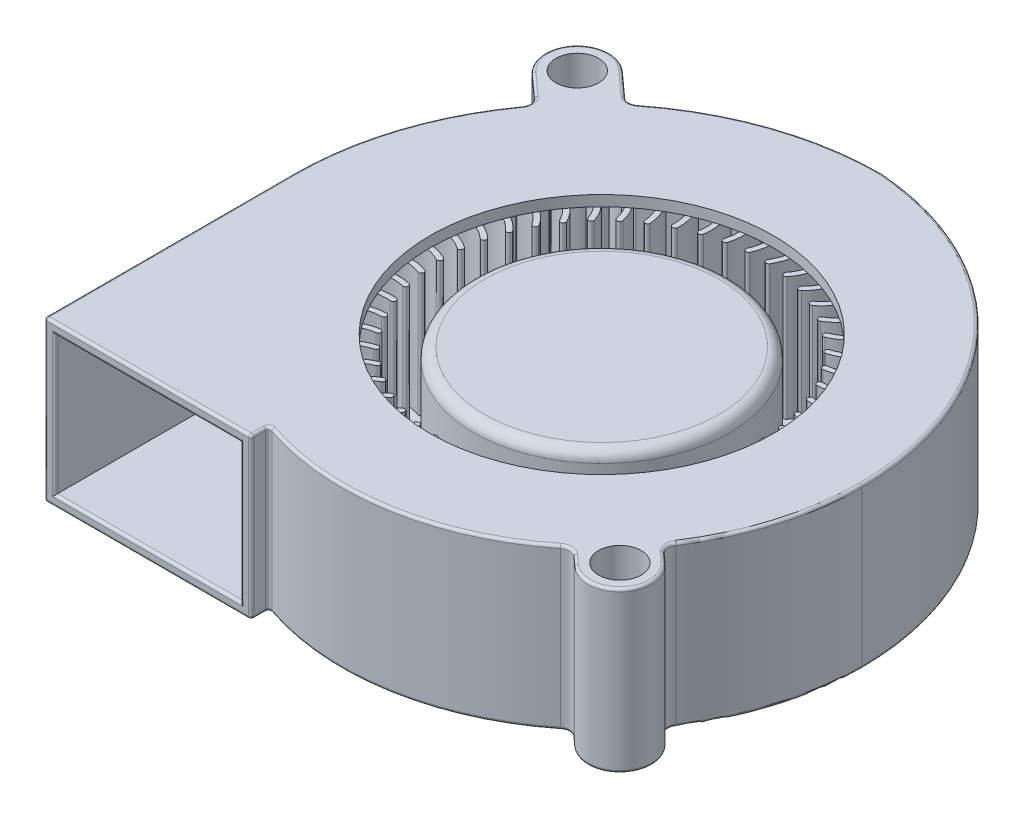
SolidWorks part; units mm, degrees
ref_plane "Front Plane" through (0, 0, 0) normal (0, 0, 1) x (1, 0, 0)
ref_plane "Top Plane" through (0, 0, 0) normal (0, 1, 0) x (1, 0, 0)
ref_plane "Right Plane" through (0, 0, 0) normal (1, 0, 0) x (0, 0, -1)
sketch "Sketch1" plane through (0, 0, 0) normal (0, 1, 0) x (1, 0, 0)
  line L0 (0, 0) -> (-22.6, 0) construction
  line L1 (0, 0) -> (-27.6, 0) construction
  line L2 (-22.6, 0) -> (-22.6, 20.3) construction
  line L4 (0, 0) -> (0, -24.7) construction
  line L5 (-8.2, -24.7) -> (-27.6, -24.7)
  line L6 (-27.6, -24.7) -> (-27.6, -1.3)
  line L7 (0, 0) -> (24.4, 0) construction
  line L8 (0, 0) -> (0, 26.3) construction
  line L10 (-8.2, -24.7) -> (-8.2, -22.9809)
  line L11 (16.5007, -19.1225) -> (17.3873, -19.9246)
  line L12 (-24.6127, 18.0754) -> (-22.5187, 16.1808)
  line L13 (-20.5873, 22.5246) -> (-18.3141, 20.468)
  line L14 (20.552, -14.6967) -> (21.4127, -15.4754)
  circle A0 centre (-22.6, 20.3) radius 2
  circle A1 centre (19.4, -17.7) radius 2
  arc A2 (17.3873, -19.9246) -> (21.4127, -15.4754) centre (19.4, -17.7) ccw
  arc A3 (0, 26.3) -> (-17.0263, 20.4224) centre (0, -1.3) ccw
  arc A4 (24.4, 0) -> (0, 26.3) centre (-1.974, 0) ccw
  arc A5 (24.4, 0) -> (20.3874, -13.4057) centre (0, 0) cw
  arc A6 (-20.5873, 22.5246) -> (-24.6127, 18.0754) centre (-22.6, 20.3) ccw
  arc A7 (15.2065, -19.082) -> (-8.2, -22.9809) centre (0, 0) cw
  circle A8 centre (0, 0) radius 16.1
  circle A9 centre (19.4, -17.7) radius 3 construction
  circle A10 centre (-22.6, 20.3) radius 3 construction
  arc A11 (-22.3788, 14.854) -> (-27.6, -1.3) centre (0, -1.3) ccw
  arc A12 (-22.3788, 14.854) -> (-22.5187, 16.1808) centre (-23.1896, 15.4392) ccw
  arc A13 (-18.3141, 20.468) -> (-17.0263, 20.4224) centre (-17.6432, 21.2095) ccw
  arc A14 (20.3874, -13.4057) -> (20.552, -14.6967) centre (21.223, -13.9551) ccw
  arc A15 (16.5007, -19.1225) -> (15.2065, -19.082) centre (15.8298, -19.864) ccw
  point P4 (-16.1, 0)
  point P29 (23.25, -20.1)
  point P32 (-16.75, 20.1)
  point P39 (19.9054, -14.1116)
  point P42 (15.8598, -18.5426)
  point P44 (0, 16.1)
  dimension "D2" = 52
  dimension "D5" = 4
  dimension "D6" = 4
  dimension "D7" = 11.5
  dimension "D12" = 19.4
  dimension "D13" = 32.2
  dimension "D15" = 1
  dimension "D8" = 44
  dimension "D3" = 45
  dimension "D4" = 47
  dimension "D9" = 10.2
  dimension "D10" = 47
  dimension "D14" = 51
  dimension "D11" = 1
extrude "BODY" add sketch "Sketch1" along normal blind 7.5 and the other way blind 7.5
shell "Shell" thickness 1 removed face at (-17.9, 0, 24.7) removed face at (0, -7.5, 16.1)
sketch "Sketch2" plane through (0, -7.5, 0) normal (0, -1, 0) x (1, 0, 0)
  circle A0 centre (0, 0) radius 20.1
extrude "Boss-Extrude2" add sketch "Sketch2" against normal blind 1
ref_plane "Plane1" through (0, -6.3, 0) normal (0, 1, 0) x (1, 0, 0)
sketch "Sketch3" plane through (0, -6.3, 0) normal (0, 1, 0) x (1, 0, 0)
  circle A0 centre (0, 0) radius 12
  dimension "D1" = 24
extrude "MOTOR" add sketch "Sketch3" along normal up to surface (12.8 mm away) separate body up to face at (-5.8935, 6.5, -0.0119)
ref_axis "Axis1" through (0, 6.5, 0) along (0, -1, 0)
fillet "Fillet1" radius 1 1 edges at (0, 6.5, -12)
fillet "Fillet2" radius 0.25 43 edges at (4.0092, -7.5, 24.0684) (16.944, -7.5, 19.5235) (21.6246, -7.5, 19.7127) (20.9824, -7.5, 15.086) (23.3753, -7.5, 6.9967) (17.3606, -7.5, -17.9377) (-9.0061, -7.5, -24.7893) (-19.4507, -7.5, -21.4963) (-24.8246, -7.5, -22.3127) (-23.5657, -7.5, -17.1281) (-26.2623, -7.5, -7.1884) (-27.6, -7.5, 13) (-19.4507, 7.5, -21.4963) (-24.8246, 7.5, -22.3127) (-26.2623, 7.5, -7.1884) (-27.6, 0, 24.7) (-26.6, 0, 24.7) (-17.9, 6.5, 24.7) (-9.2, 0, 24.7) (-17.9, -6.5, 24.7) (-17.9, -7.5, 24.7) (-8.2, -7.5, 23.8404) (-8.2, 0, 22.9809) (-8.2, 0, 24.7) (-17.9, 7.5, 24.7) (-8.2, 7.5, 23.8404) (4.0092, 7.5, 24.0684) (16.944, 7.5, 19.5235) (21.6246, 7.5, 19.7127) (20.9824, 7.5, 15.086) (23.3753, 7.5, 6.9967) (17.3606, 7.5, -17.9377) (-9.0061, 7.5, -24.7893) (-23.5657, 7.5, -17.1281) (-27.6, 7.5, 13) (15.8611, -7.5, 18.8645) (20.231, -7.5, 14.0816) (-17.6785, -7.5, -20.2101) (-22.1951, -7.5, -15.5441) (15.8611, 7.5, 18.8645) (20.231, 7.5, 14.0816) (-17.6785, 7.5, -20.2101) (-22.1951, 7.5, -15.5441)
sketch "Sketch9" plane through (0, -6.3, 0) normal (0, 1, 0) x (1, 0, 0)
  circle A0 centre (0, 0) radius 19
  dimension "D1" = 38
extrude "BLADE BASE" add sketch "Sketch9" along normal blind 1 separate body
sketch "Sketch10" plane through (0, -5.3, 0) normal (0, 1, 0) x (1, 0, 0)
  line L0 (0, 0) -> (-18.8663, 0) construction
  line L1 (-16.8663, 0.5) -> (-16.8663, 0) construction
  line L2 (-14.8663, 0) -> (-15.1016, -0.4412) construction
  line L3 (-18.8663, 0) -> (-18.6311, -0.4412) construction
  arc A1 (-18.8663, 0) -> (-14.8663, 0) centre (-16.8663, -3.75) cw
  arc A2 (-18.6311, -0.4412) -> (-15.1016, -0.4412) centre (-16.8663, -3.75) cw
  arc A3 (-18.8663, 0) -> (-18.6311, -0.4412) centre (-18.7487, -0.2206) ccw
  arc A4 (-15.1016, -0.4412) -> (-14.8663, 0) centre (-14.984, -0.2206) ccw
  circle A5 centre (0, 0) radius 19 construction
  arc A6 (-18.7176, 2.3646) -> (-18.5394, 1.8974) centre (-18.6285, 2.131) ccw
  arc A7 (-18.7176, 2.3646) -> (-14.7491, 1.8632) centre (-17.2034, -1.6065) cw
  arc A8 (-18.5394, 1.8974) -> (-15.0379, 1.455) centre (-17.2034, -1.6065) cw
  arc A9 (-15.0379, 1.455) -> (-14.7491, 1.8632) centre (-14.8935, 1.6591) ccw
  arc A10 (-18.2736, 4.6919) -> (-18.1554, 4.206) centre (-18.2145, 4.449) ccw
  arc A11 (-18.2736, 4.6919) -> (-14.3993, 3.6971) centre (-17.269, 0.5623) cw
  arc A12 (-18.1554, 4.206) -> (-14.7369, 3.3283) centre (-17.269, 0.5623) cw
  arc A13 (-14.7369, 3.3283) -> (-14.3993, 3.6971) centre (-14.5681, 3.5127) ccw
  arc A14 (-17.5415, 6.9452) -> (-17.4851, 6.4484) centre (-17.5133, 6.6968) ccw
  arc A15 (-17.5415, 6.9452) -> (-13.8224, 5.4727) centre (-17.0624, 2.7223) cw
  arc A16 (-17.4851, 6.4484) -> (-14.2036, 5.1491) centre (-17.0624, 2.7223) cw
  arc A17 (-14.2036, 5.1491) -> (-13.8224, 5.4727) centre (-14.013, 5.3109) ccw
  arc A18 (-16.5327, 9.0889) -> (-16.5391, 8.589) centre (-16.5359, 8.839) ccw
  arc A19 (-16.5327, 9.0889) -> (-13.0275, 7.1619) centre (-16.5867, 4.8393) cw
  arc A20 (-16.5391, 8.589) -> (-13.4462, 6.8887) centre (-16.5867, 4.8393) cw
  arc A21 (-13.4462, 6.8887) -> (-13.0275, 7.1619) centre (-13.2368, 7.0253) ccw
  arc A22 (-15.2632, 11.0894) -> (-15.3322, 10.5941) centre (-15.2977, 10.8418) ccw
  arc A23 (-15.2632, 11.0894) -> (-12.0271, 8.7382) centre (-15.8494, 6.88) cw
  arc A24 (-15.3322, 10.5941) -> (-12.4768, 8.5196) centre (-15.8494, 6.88) cw
  arc A25 (-12.4768, 8.5196) -> (-12.0271, 8.7382) centre (-12.252, 8.6289) ccw
  arc A26 (-13.753, 12.9149) -> (-13.8835, 12.4322) centre (-13.8182, 12.6736) ccw
  arc A27 (-13.753, 12.9149) -> (-10.8371, 10.1767) centre (-14.8621, 8.8122) cw
  arc A28 (-13.8835, 12.4322) -> (-11.3106, 10.0162) centre (-14.8621, 8.8122) cw
  arc A29 (-11.3106, 10.0162) -> (-10.8371, 10.1767) centre (-11.0739, 10.0964) ccw
  arc A30 (-12.0259, 14.5368) -> (-12.2158, 14.0743) centre (-12.1208, 14.3055) ccw
  arc A31 (-12.0259, 14.5368) -> (-9.4762, 11.4547) centre (-13.6404, 10.6054) cw
  arc A32 (-12.2158, 14.0743) -> (-9.9661, 11.3548) centre (-13.6404, 10.6054) cw
  arc A33 (-9.9661, 11.3548) -> (-9.4762, 11.4547) centre (-9.7211, 11.4048) ccw
  arc A34 (-10.1091, 15.9294) -> (-10.3555, 15.4943) centre (-10.2323, 15.7119) ccw
  arc A35 (-10.1091, 15.9294) -> (-7.9658, 12.5521) centre (-12.2037, 12.2314) cw
  arc A36 (-10.3555, 15.4943) -> (-8.4644, 12.5143) centre (-12.2037, 12.2314) cw
  arc A37 (-8.4644, 12.5143) -> (-7.9658, 12.5521) centre (-8.2151, 12.5332) ccw
  arc A38 (-8.0329, 17.0708) -> (-8.3319, 16.67) centre (-8.1824, 16.8704) ccw
  arc A39 (-8.0329, 17.0708) -> (-6.3298, 13.4515) centre (-10.5744, 13.6645) cw
  arc A40 (-8.3319, 16.67) -> (-6.8292, 13.4765) centre (-10.5744, 13.6645) cw
  arc A41 (-6.8292, 13.4765) -> (-6.3298, 13.4515) centre (-6.5795, 13.464) ccw
  arc A42 (-5.83, 17.943) -> (-6.1769, 17.5829) centre (-6.0035, 17.7629) ccw
  arc A43 (-5.83, 17.943) -> (-4.594, 14.1387) centre (-8.7785, 14.882) cw
  arc A44 (-6.1769, 17.5829) -> (-5.0862, 14.2262) centre (-8.7785, 14.882) cw
  arc A45 (-5.0862, 14.2262) -> (-4.594, 14.1387) centre (-4.8401, 14.1825) ccw
  arc A46 (-3.5352, 18.5322) -> (-3.9245, 18.2184) centre (-3.7298, 18.3753) ccw
  arc A47 (-3.5352, 18.5322) -> (-2.7857, 14.603) centre (-6.844, 15.8649) cw
  arc A48 (-3.9245, 18.2184) -> (-3.2631, 14.7515) centre (-6.844, 15.8649) cw
  arc A49 (-3.2631, 14.7515) -> (-2.7857, 14.603) centre (-3.0244, 14.6773) ccw
  arc A50 (-1.1846, 18.8291) -> (-1.6102, 18.5666) centre (-1.3974, 18.6979) ccw
  arc A51 (-1.1846, 18.8291) -> (-0.9335, 14.837) centre (-4.8016, 16.5976) cw
  arc A52 (-1.6102, 18.5666) -> (-1.3885, 15.0441) centre (-4.8016, 16.5976) cw
  arc A53 (-1.3885, 15.0441) -> (-0.9335, 14.837) centre (-1.161, 14.9406) ccw
  arc A54 (1.1846, 18.8291) -> (0.7295, 18.622) centre (0.9571, 18.7256) ccw
  arc A55 (1.1846, 18.8291) -> (0.9335, 14.837) centre (-2.6836, 17.0685) cw
  arc A56 (0.7295, 18.622) -> (0.5079, 15.0995) centre (-2.6836, 17.0685) cw
  arc A57 (0.5079, 15.0995) -> (0.9335, 14.837) centre (0.7207, 14.9683) ccw
  arc A58 (3.5352, 18.5322) -> (3.0577, 18.3837) centre (3.2965, 18.4579) ccw
  arc A59 (3.5352, 18.5322) -> (2.7857, 14.603) centre (-0.5231, 17.2703) cw
  arc A60 (3.0577, 18.3837) -> (2.3964, 14.9168) centre (-0.5231, 17.2703) cw
  arc A61 (2.3964, 14.9168) -> (2.7857, 14.603) centre (2.591, 14.7599) ccw
  arc A62 (5.83, 17.943) -> (5.3377, 17.8555) centre (5.5839, 17.8992) ccw
  arc A63 (5.83, 17.943) -> (4.594, 14.1387) centre (1.6455, 17.1997) cw
  arc A64 (5.3377, 17.8555) -> (4.2471, 14.4988) centre (1.6455, 17.1997) cw
  arc A65 (4.2471, 14.4988) -> (4.594, 14.1387) centre (4.4205, 14.3188) ccw
  arc A66 (8.0329, 17.0708) -> (7.5335, 17.0457) centre (7.7832, 17.0583) ccw
  arc A67 (8.0329, 17.0708) -> (6.3298, 13.4515) centre (3.7882, 16.8578) cw
  arc A68 (7.5335, 17.0457) -> (6.0308, 13.8522) centre (3.7882, 16.8578) cw
  arc A69 (6.0308, 13.8522) -> (6.3298, 13.4515) centre (6.1803, 13.6518) ccw
  arc A70 (10.1091, 15.9294) -> (9.6105, 15.9671) centre (9.8598, 15.9483) ccw
  arc A71 (10.1091, 15.9294) -> (7.9658, 12.5521) centre (5.8712, 16.2501) cw
  arc A72 (9.6105, 15.9671) -> (7.7194, 12.9871) centre (5.8712, 16.2501) cw
  arc A73 (7.7194, 12.9871) -> (7.9658, 12.5521) centre (7.8426, 12.7696) ccw
  arc A74 (12.0259, 14.5368) -> (11.5359, 14.6367) centre (11.7809, 14.5867) ccw
  arc A75 (12.0259, 14.5368) -> (9.4762, 11.4547) centre (7.8616, 15.3861) cw
  arc A76 (11.5359, 14.6367) -> (9.2862, 11.9172) centre (7.8616, 15.3861) cw
  arc A77 (9.2862, 11.9172) -> (9.4762, 11.4547) centre (9.3812, 11.686) ccw
  arc A78 (13.753, 12.9149) -> (13.2794, 13.0754) centre (13.5162, 12.9952) ccw
  arc A79 (13.753, 12.9149) -> (10.8371, 10.1767) centre (9.728, 14.2794) cw
  arc A80 (13.2794, 13.0754) -> (10.7066, 10.6594) centre (9.728, 14.2794) cw
  arc A81 (10.7066, 10.6594) -> (10.8371, 10.1767) centre (10.7719, 10.4181) ccw
  arc A82 (15.2632, 11.0894) -> (14.8135, 11.308) centre (15.0384, 11.1987) ccw
  arc A83 (15.2632, 11.0894) -> (12.0271, 8.7382) centre (11.441, 12.9476) cw
  arc A84 (14.8135, 11.308) -> (11.9582, 9.2334) centre (11.441, 12.9476) cw
  arc A85 (11.9582, 9.2334) -> (12.0271, 8.7382) centre (11.9926, 8.9858) ccw
  arc A86 (16.5327, 9.0889) -> (16.114, 9.3622) centre (16.3233, 9.2256) ccw
  arc A87 (16.5327, 9.0889) -> (13.0275, 7.1619) centre (12.9735, 11.4116) cw
  arc A88 (16.114, 9.3622) -> (13.0211, 7.6619) centre (12.9735, 11.4116) cw
  arc A89 (13.0211, 7.6619) -> (13.0275, 7.1619) centre (13.0243, 7.4119) ccw
  arc A90 (17.5415, 6.9452) -> (17.1603, 7.2687) centre (17.3509, 7.107) ccw
  arc A91 (17.5415, 6.9452) -> (13.8224, 5.4727) centre (14.3015, 9.6956) cw
  arc A92 (17.1603, 7.2687) -> (13.8787, 5.9695) centre (14.3015, 9.6956) cw
  arc A93 (13.8787, 5.9695) -> (13.8224, 5.4727) centre (13.8506, 5.7211) ccw
  arc A94 (18.2736, 4.6919) -> (17.936, 5.0607) centre (18.1048, 4.8763) ccw
  arc A95 (18.2736, 4.6919) -> (14.3993, 3.6971) centre (15.4039, 7.8267) cw
  arc A96 (17.936, 5.0607) -> (14.5175, 4.1829) centre (15.4039, 7.8267) cw
  arc A97 (14.5175, 4.1829) -> (14.3993, 3.6971) centre (14.4584, 3.94) ccw
  arc A98 (18.7176, 2.3646) -> (18.4288, 2.7728) centre (18.5732, 2.5687) ccw
  arc A99 (18.7176, 2.3646) -> (14.7491, 1.8632) centre (16.2634, 5.8343) cw
  arc A100 (18.4288, 2.7728) -> (14.9273, 2.3304) centre (16.2634, 5.8343) cw
  arc A101 (14.9273, 2.3304) -> (14.7491, 1.8632) centre (14.8382, 2.0968) ccw
  arc A102 (18.8663, 0) -> (18.6311, 0.4412) centre (18.7487, 0.2206) ccw
  arc A103 (18.8663, 0) -> (14.8663, 0) centre (16.8663, 3.75) cw
  arc A104 (18.6311, 0.4412) -> (15.1016, 0.4412) centre (16.8663, 3.75) cw
  arc A105 (15.1016, 0.4412) -> (14.8663, 0) centre (14.984, 0.2206) ccw
  arc A106 (18.7176, -2.3646) -> (18.5394, -1.8974) centre (18.6285, -2.131) ccw
  arc A107 (18.7176, -2.3646) -> (14.7491, -1.8632) centre (17.2034, 1.6065) cw
  arc A108 (18.5394, -1.8974) -> (15.0379, -1.455) centre (17.2034, 1.6065) cw
  arc A109 (15.0379, -1.455) -> (14.7491, -1.8632) centre (14.8935, -1.6591) ccw
  arc A110 (18.2736, -4.6919) -> (18.1554, -4.206) centre (18.2145, -4.449) ccw
  arc A111 (18.2736, -4.6919) -> (14.3993, -3.6971) centre (17.269, -0.5623) cw
  arc A112 (18.1554, -4.206) -> (14.7369, -3.3283) centre (17.269, -0.5623) cw
  arc A113 (14.7369, -3.3283) -> (14.3993, -3.6971) centre (14.5681, -3.5127) ccw
  arc A114 (17.5415, -6.9452) -> (17.4851, -6.4484) centre (17.5133, -6.6968) ccw
  arc A115 (17.5415, -6.9452) -> (13.8224, -5.4727) centre (17.0624, -2.7223) cw
  arc A116 (17.4851, -6.4484) -> (14.2036, -5.1491) centre (17.0624, -2.7223) cw
  arc A117 (14.2036, -5.1491) -> (13.8224, -5.4727) centre (14.013, -5.3109) ccw
  arc A118 (16.5327, -9.0889) -> (16.5391, -8.589) centre (16.5359, -8.839) ccw
  arc A119 (16.5327, -9.0889) -> (13.0275, -7.1619) centre (16.5867, -4.8393) cw
  arc A120 (16.5391, -8.589) -> (13.4462, -6.8887) centre (16.5867, -4.8393) cw
  arc A121 (13.4462, -6.8887) -> (13.0275, -7.1619) centre (13.2368, -7.0253) ccw
  arc A122 (15.2632, -11.0894) -> (15.3322, -10.5941) centre (15.2977, -10.8418) ccw
  arc A123 (15.2632, -11.0894) -> (12.0271, -8.7382) centre (15.8494, -6.88) cw
  arc A124 (15.3322, -10.5941) -> (12.4768, -8.5196) centre (15.8494, -6.88) cw
  arc A125 (12.4768, -8.5196) -> (12.0271, -8.7382) centre (12.252, -8.6289) ccw
  arc A126 (13.753, -12.9149) -> (13.8835, -12.4322) centre (13.8182, -12.6736) ccw
  arc A127 (13.753, -12.9149) -> (10.8371, -10.1767) centre (14.8621, -8.8122) cw
  arc A128 (13.8835, -12.4322) -> (11.3106, -10.0162) centre (14.8621, -8.8122) cw
  arc A129 (11.3106, -10.0162) -> (10.8371, -10.1767) centre (11.0739, -10.0964) ccw
  arc A130 (12.0259, -14.5368) -> (12.2158, -14.0743) centre (12.1208, -14.3055) ccw
  arc A131 (12.0259, -14.5368) -> (9.4762, -11.4547) centre (13.6404, -10.6054) cw
  arc A132 (12.2158, -14.0743) -> (9.9661, -11.3548) centre (13.6404, -10.6054) cw
  arc A133 (9.9661, -11.3548) -> (9.4762, -11.4547) centre (9.7211, -11.4048) ccw
  arc A134 (10.1091, -15.9294) -> (10.3555, -15.4943) centre (10.2323, -15.7119) ccw
  arc A135 (10.1091, -15.9294) -> (7.9658, -12.5521) centre (12.2037, -12.2314) cw
  arc A136 (10.3555, -15.4943) -> (8.4644, -12.5143) centre (12.2037, -12.2314) cw
  arc A137 (8.4644, -12.5143) -> (7.9658, -12.5521) centre (8.2151, -12.5332) ccw
  arc A138 (8.0329, -17.0708) -> (8.3319, -16.67) centre (8.1824, -16.8704) ccw
  arc A139 (8.0329, -17.0708) -> (6.3298, -13.4515) centre (10.5744, -13.6645) cw
  arc A140 (8.3319, -16.67) -> (6.8292, -13.4765) centre (10.5744, -13.6645) cw
  arc A141 (6.8292, -13.4765) -> (6.3298, -13.4515) centre (6.5795, -13.464) ccw
  arc A142 (5.83, -17.943) -> (6.1769, -17.5829) centre (6.0035, -17.7629) ccw
  arc A143 (5.83, -17.943) -> (4.594, -14.1387) centre (8.7785, -14.882) cw
  arc A144 (6.1769, -17.5829) -> (5.0862, -14.2262) centre (8.7785, -14.882) cw
  arc A145 (5.0862, -14.2262) -> (4.594, -14.1387) centre (4.8401, -14.1825) ccw
  arc A146 (3.5352, -18.5322) -> (3.9245, -18.2184) centre (3.7298, -18.3753) ccw
  arc A147 (3.5352, -18.5322) -> (2.7857, -14.603) centre (6.844, -15.8649) cw
  arc A148 (3.9245, -18.2184) -> (3.2631, -14.7515) centre (6.844, -15.8649) cw
  arc A149 (3.2631, -14.7515) -> (2.7857, -14.603) centre (3.0244, -14.6773) ccw
  arc A150 (1.1846, -18.8291) -> (1.6102, -18.5666) centre (1.3974, -18.6979) ccw
  arc A151 (1.1846, -18.8291) -> (0.9335, -14.837) centre (4.8016, -16.5976) cw
  arc A152 (1.6102, -18.5666) -> (1.3885, -15.0441) centre (4.8016, -16.5976) cw
  arc A153 (1.3885, -15.0441) -> (0.9335, -14.837) centre (1.161, -14.9406) ccw
  arc A154 (-1.1846, -18.8291) -> (-0.7295, -18.622) centre (-0.9571, -18.7256) ccw
  arc A155 (-1.1846, -18.8291) -> (-0.9335, -14.837) centre (2.6836, -17.0685) cw
  arc A156 (-0.7295, -18.622) -> (-0.5079, -15.0995) centre (2.6836, -17.0685) cw
  arc A157 (-0.5079, -15.0995) -> (-0.9335, -14.837) centre (-0.7207, -14.9683) ccw
  arc A158 (-3.5352, -18.5322) -> (-3.0577, -18.3837) centre (-3.2965, -18.4579) ccw
  arc A159 (-3.5352, -18.5322) -> (-2.7857, -14.603) centre (0.5231, -17.2703) cw
  arc A160 (-3.0577, -18.3837) -> (-2.3964, -14.9168) centre (0.5231, -17.2703) cw
  arc A161 (-2.3964, -14.9168) -> (-2.7857, -14.603) centre (-2.591, -14.7599) ccw
  arc A162 (-5.83, -17.943) -> (-5.3377, -17.8555) centre (-5.5839, -17.8992) ccw
  arc A163 (-5.83, -17.943) -> (-4.594, -14.1387) centre (-1.6455, -17.1997) cw
  arc A164 (-5.3377, -17.8555) -> (-4.2471, -14.4988) centre (-1.6455, -17.1997) cw
  arc A165 (-4.2471, -14.4988) -> (-4.594, -14.1387) centre (-4.4205, -14.3188) ccw
  arc A166 (-8.0329, -17.0708) -> (-7.5335, -17.0457) centre (-7.7832, -17.0583) ccw
  arc A167 (-8.0329, -17.0708) -> (-6.3298, -13.4515) centre (-3.7882, -16.8578) cw
  arc A168 (-7.5335, -17.0457) -> (-6.0308, -13.8522) centre (-3.7882, -16.8578) cw
  arc A169 (-6.0308, -13.8522) -> (-6.3298, -13.4515) centre (-6.1803, -13.6518) ccw
  arc A170 (-10.1091, -15.9294) -> (-9.6105, -15.9671) centre (-9.8598, -15.9483) ccw
  arc A171 (-10.1091, -15.9294) -> (-7.9658, -12.5521) centre (-5.8712, -16.2501) cw
  arc A172 (-9.6105, -15.9671) -> (-7.7194, -12.9871) centre (-5.8712, -16.2501) cw
  arc A173 (-7.7194, -12.9871) -> (-7.9658, -12.5521) centre (-7.8426, -12.7696) ccw
  arc A174 (-12.0259, -14.5368) -> (-11.5359, -14.6367) centre (-11.7809, -14.5867) ccw
  arc A175 (-12.0259, -14.5368) -> (-9.4762, -11.4547) centre (-7.8616, -15.3861) cw
  arc A176 (-11.5359, -14.6367) -> (-9.2862, -11.9172) centre (-7.8616, -15.3861) cw
  arc A177 (-9.2862, -11.9172) -> (-9.4762, -11.4547) centre (-9.3812, -11.686) ccw
  arc A178 (-13.753, -12.9149) -> (-13.2794, -13.0754) centre (-13.5162, -12.9952) ccw
  arc A179 (-13.753, -12.9149) -> (-10.8371, -10.1767) centre (-9.728, -14.2794) cw
  arc A180 (-13.2794, -13.0754) -> (-10.7066, -10.6594) centre (-9.728, -14.2794) cw
  arc A181 (-10.7066, -10.6594) -> (-10.8371, -10.1767) centre (-10.7719, -10.4181) ccw
  arc A182 (-15.2632, -11.0894) -> (-14.8135, -11.308) centre (-15.0384, -11.1987) ccw
  arc A183 (-15.2632, -11.0894) -> (-12.0271, -8.7382) centre (-11.441, -12.9476) cw
  arc A184 (-14.8135, -11.308) -> (-11.9582, -9.2334) centre (-11.441, -12.9476) cw
  arc A185 (-11.9582, -9.2334) -> (-12.0271, -8.7382) centre (-11.9926, -8.9858) ccw
  arc A186 (-16.5327, -9.0889) -> (-16.114, -9.3622) centre (-16.3233, -9.2256) ccw
  arc A187 (-16.5327, -9.0889) -> (-13.0275, -7.1619) centre (-12.9735, -11.4116) cw
  arc A188 (-16.114, -9.3622) -> (-13.0211, -7.6619) centre (-12.9735, -11.4116) cw
  arc A189 (-13.0211, -7.6619) -> (-13.0275, -7.1619) centre (-13.0243, -7.4119) ccw
  arc A190 (-17.5415, -6.9452) -> (-17.1603, -7.2687) centre (-17.3509, -7.107) ccw
  arc A191 (-17.5415, -6.9452) -> (-13.8224, -5.4727) centre (-14.3015, -9.6956) cw
  arc A192 (-17.1603, -7.2687) -> (-13.8787, -5.9695) centre (-14.3015, -9.6956) cw
  arc A193 (-13.8787, -5.9695) -> (-13.8224, -5.4727) centre (-13.8506, -5.7211) ccw
  arc A194 (-18.2736, -4.6919) -> (-17.936, -5.0607) centre (-18.1048, -4.8763) ccw
  arc A195 (-18.2736, -4.6919) -> (-14.3993, -3.6971) centre (-15.4039, -7.8267) cw
  arc A196 (-17.936, -5.0607) -> (-14.5175, -4.1829) centre (-15.4039, -7.8267) cw
  arc A197 (-14.5175, -4.1829) -> (-14.3993, -3.6971) centre (-14.4584, -3.94) ccw
  arc A198 (-18.7176, -2.3646) -> (-18.4288, -2.7728) centre (-18.5732, -2.5687) ccw
  arc A199 (-18.7176, -2.3646) -> (-14.7491, -1.8632) centre (-16.2634, -5.8343) cw
  arc A200 (-18.4288, -2.7728) -> (-14.9273, -2.3304) centre (-16.2634, -5.8343) cw
  arc A201 (-14.9273, -2.3304) -> (-14.7491, -1.8632) centre (-14.8382, -2.0968) ccw
  point P4 (-19.3848, 3.1295)
  point P5 (-18.011, 2.0524)
  point P6 (-16.2745, 2.2323)
  point P7 (-18.011, 2.0524)
  point P8 (-19.1881, 2.9752)
  point P9 (-16.5232, 2.2065)
  point P417 (0, 0)
  dimension "D2" = 0.5
  dimension "D1" = 4
  dimension "D3" = 0.5
  dimension "D4" = 50
extrude "BLADE" add sketch "Sketch10" along normal offset from surface (11.6 mm away) 0.2 separate body up to face at (-5.8935, 6.5, -0.0432)
ref_plane "Plane2" through (-17.9, 0, 0) normal (-1, 0, 0) x (0, 0, 1)
ref_plane "Plane3" through (0, 0, 0) normal (0, 1, 0) x (1, 0, 0)
